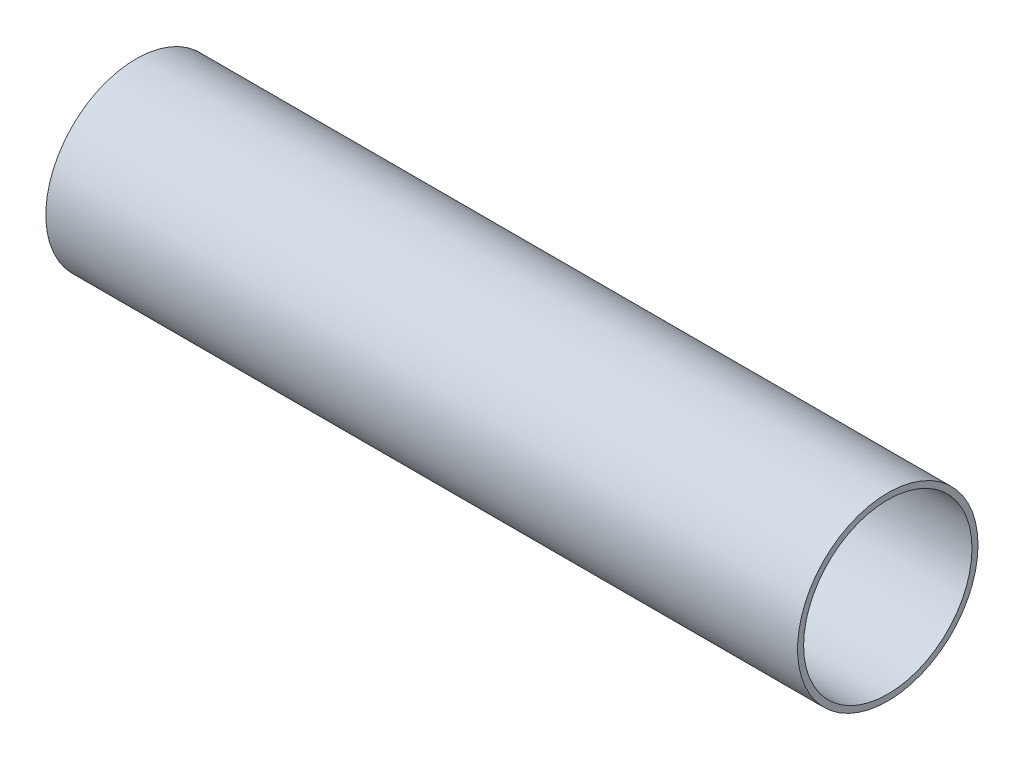
SolidWorks part; units mm, degrees
material "炭素鋼(普通)"
ref_plane "HOR" through (0, 0, 0) normal (0, 0, 1) x (1, 0, 0)
ref_plane "VERT" through (0, 0, 0) normal (0, 1, 0) x (1, 0, 0)
ref_plane "CTR" through (0, 0, 0) normal (1, 0, 0) x (0, 0, -1)
ref_axis "A_X" through (88.99, 0, 0) along (-1, 0, 0)
ref_axis "A_Y" through (0, 55, 0) along (0, -1, 0)
ref_axis "A_Z" through (0, 0, 55) along (0, 0, -1)
sketch3d "PNT_CG"
  point P0 (0, 0, 0)
sketch "Sketch1" plane through (0, 0, 0) normal (1, 0, 0) x (0, 0, -1)
  circle A0 centre (0, 0) radius 30
  dimension "D1" = 60
extrude "Boss-Extrude1" add sketch "Sketch1" along normal blind 250
sketch "Sketch2" plane through (250, 0, 0) normal (1, 0, 0) x (0, 0, -1)
  circle A0 centre (0, 0) radius 28
  dimension "D1" = 56
extrude "Cut-Extrude1" cut sketch "Sketch2" against normal blind 250
